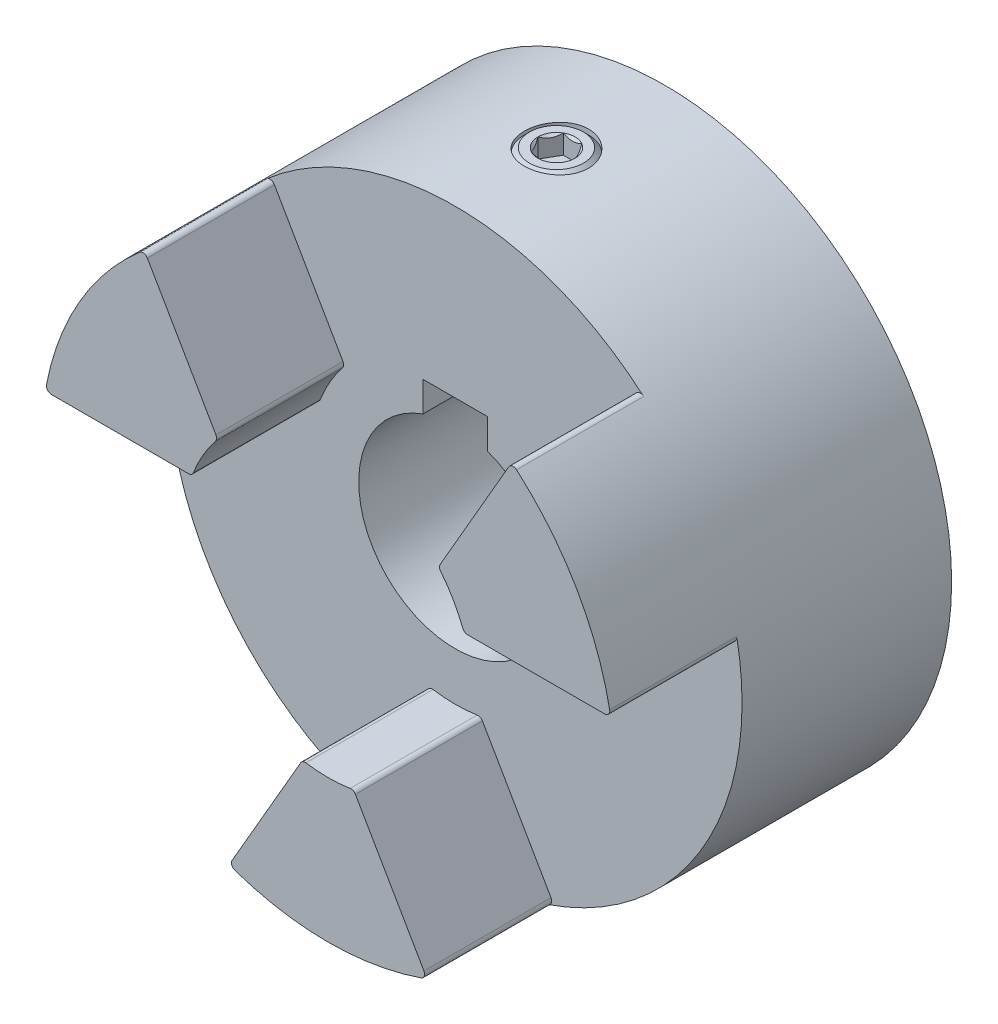
SolidWorks part; units mm, degrees
ref_plane "Front" through (0, 0, 0) normal (0, 0, 1) x (1, 0, 0)
ref_plane "Top" through (0, 0, 0) normal (0, 1, 0) x (1, 0, 0)
ref_plane "Right" through (0, 0, 0) normal (1, 0, 0) x (0, 0, -1)
sketch "Sketch3" plane through (0, 0, 0) normal (1, 0, 0) x (0, 0, -1)
  line L0 (27.3844, 0) -> (-27.3844, 0) construction
  circle A0 centre (0, 0) radius 5.1149 construction
  circle A1 centre (0, 0) radius 9 construction
  circle A2 centre (0, 0) radius 26.7891 construction
  point P7 (0, 5.1149)
  point P8 (0, -5.1149)
  point P9 (0, 9)
  point P10 (0, -9)
  point P11 (0, 26.7891)
  point P12 (0, -26.7891)
  point P13 (6.7469, 0)
  point P14 (-5.1149, 0)
  point P15 (5.1149, 0)
  point P16 (-5.1149, 26.7891)
  point P17 (27.3844, 26.7891)
  point P18 (6.7469, 26.7891)
  dimension "OD" = 53.5781
  dimension "Shaft Dia" = 18
  dimension "Overall Lg" = 54.7687
  dimension "Bore Depth" = 20.6375
  dimension "Lug Lg" = 11.8618
sketch "Sketch1" plane through (0, 0, 0) normal (0, 0, 1) x (1, 0, 0)
  circle A0 centre (0, 0) radius 26.7891
  circle A1 centre (0, 0) radius 9 construction
extrude "Boss-Extrude1" add sketch "Sketch1" against normal up to vertex (27.3844 mm away) from vertex up to point (0, 0, -27.3844) starting at point (0, 0, -6.7469)
sketch "Sketch10" [suppressed] plane through (0, 0, -3.5719) normal (0, 0, 1) x (1, 0, 0)
  arc A14 (-1.0963, -4.1108) -> (1.0963, -4.1108) centre (0, 0) ccw
  arc A15 (-3.4409, -7.1529) -> (-1.0963, -4.1108) centre (-9.5758, 0) ccw
  arc A19 (1.0963, -4.1108) -> (3.4409, -7.1529) centre (9.5758, 0) ccw
  circle A32 centre (0, 0) radius 7.9375 construction
  arc A33 (-3.4409, -7.1529) -> (3.4409, -7.1529) centre (0, 0) ccw
  point P0 (0, -4.2545)
  point P1 (0, -7.9375)
  dimension "D1" = 3.683
  dimension "D4" = 9.4234
  dimension "D2" = 6.8819
  dimension "D3" = 2.1926
extrude "Boss-Extrude4" [suppressed] add sketch "Sketch10" along normal up to vertex up to point (0, 0, 5.1149)
fillet "Fillet2" [suppressed] radius 0.381
other "Move Face3" [suppressed] parameters "D1"=90
pattern_circular "CirPattern2" [suppressed] count 2 over 360 of bodies 116
sketch "Sketch11" [suppressed] plane through (0, 0, -5.9531) normal (0, 0, 1) x (1, 0, 0)
  arc A0 (-1.5825, -7.8835) -> (1.5738, -7.8835) centre (-0.0044, -0.0397) ccw
  arc A1 (-1.5825, -7.8835) -> (-2.9616, -8.354) centre (-1.8681, -9.3029) ccw
  arc A2 (-2.9616, -8.354) -> (-4.9794, -11.8231) centre (5.1535, -15.3956) ccw
  arc A3 (-4.9794, -11.8231) -> (-4.4308, -12.9555) centre (-4.1442, -12.1175) ccw
  arc A4 (-4.4308, -12.9555) -> (4.4176, -12.96) centre (0, 0) ccw
  arc A5 (4.4176, -12.96) -> (4.9692, -11.8231) centre (4.1308, -12.1185) ccw
  arc A6 (4.9692, -11.8231) -> (2.9523, -8.354) centre (-5.1643, -15.3938) ccw
  arc A7 (2.9523, -8.354) -> (1.5738, -7.8835) centre (1.8592, -9.3021) ccw
  circle A8 centre (0, 0) radius 13.6922 construction
  point P18 (-0.007, -13.6922)
  point P19 (-0.0044, -8.0407)
  dimension "D1" = 1.4478
  dimension "D2" = 8.001
  dimension "D3" = 10.7442
  dimension "D4" = 0.889
  dimension "D9" = 5.6515
  dimension "D5" = 5.072
  dimension "D6" = 3.1563
  dimension "D7" = 5.9139
  dimension "D8" = 9.9486
extrude "Boss-Extrude5" [suppressed] add sketch "Sketch11" along normal up to vertex up to point (0, 0, 5.1149)
other "Move Face1" [suppressed] parameters "D1"=90
pattern_circular "CirPattern3" [suppressed] count 2 over 360 of bodies 118
sketch "Sketch12" [suppressed] plane through (0, 0, -6.1516) normal (0, 0, 1) x (1, 0, 0)
  line L0 (-5.1097, -10.267) -> (-8.533, -13.6894)
  line L1 (8.533, -13.6894) -> (5.1097, -10.267)
  arc A0 (-2.3442, -9.4968) -> (2.3442, -9.4968) centre (0, 0) ccw
  arc A1 (-2.3442, -9.4968) -> (-5.1097, -10.267) centre (-3.0443, -12.333) ccw
  arc A2 (-8.533, -13.6894) -> (-8.3299, -15.1215) centre (-7.8934, -14.3292) ccw
  arc A3 (-8.3299, -15.1215) -> (8.3299, -15.1215) centre (0, 0) ccw
  arc A4 (8.3299, -15.1215) -> (8.533, -13.6894) centre (7.8934, -14.3292) ccw
  arc A5 (5.1097, -10.267) -> (2.3442, -9.4968) centre (3.0443, -12.333) ccw
  circle A6 centre (0, 0) radius 17.2641 construction
  point P16 (0, -9.7819)
  point P17 (0, -17.2641)
  dimension "D1" = 7.4822
  dimension "D2" = 10.2193
  dimension "D3" = 4.6884
  dimension "D4" = 17.066
  dimension "D5" = 16.6598
extrude "Boss-Extrude6" [suppressed] add sketch "Sketch12" along normal up to vertex up to point (0, 0, 5.1149)
other "Move Face2" [suppressed] parameters "D1"=90
pattern_circular "CirPattern4" [suppressed] count 2 over 360 of bodies 120
sketch "Sketch2" plane through (0, 0, -6.7469) normal (0, 0, 1) x (1, 0, 0)
  line L0 (-9.2385, -25.1456) -> (-2.385, -13.2749)
  line L2 (2.385, -13.2749) -> (9.2385, -25.1456)
  circle A0 centre (0, 0) radius 26.7891 construction
  arc A1 (-9.2385, -25.1456) -> (9.2385, -25.1456) centre (0, 0) ccw
  arc A2 (-2.385, -13.2749) -> (2.385, -13.2749) centre (0, 0) ccw
  circle A3 centre (0, 0) radius 4.572 construction
  dimension "Spider Inner body Dia" = 26.9748
  dimension "Spider Leg Thickness" = 9.144
  dimension "D4" = 4.7699
  dimension "D1" = 60
extrude "Boss-Extrude2" add sketch "Sketch2" along normal up to vertex (11.8618 mm away) up to point (0, 0, 5.1149)
fillet "Fillet1" radius 0.477 4 edges at (2.385, -13.2749, -0.816) (-2.385, -13.2749, -0.816)
pattern_circular "CirPattern1" count 3 over 360 about axis through (0, 0, -27.3844) along (0, 0, 1) of "Boss-Extrude2", "Fillet1"
sketch "Sketch15" plane through (0, 0, 0) normal (0, 0, 1) x (1, 0, 0)
  circle A0 centre (0, 0) radius 9
extrude "Cut-Extrude5" cut sketch "Sketch15" against normal through all and the other way through all
chamfer "Chamfer1" distance 1.0716 angle 56 2 edges at (26.7891, 0, -27.3844) (9, 0, -27.3844) first distance on face at (26.7891, 0, -27.3844) first distance on face at (9, 0, -6.7469)
sketch "Sketch4" plane through (0, 0, 0) normal (0, 0, 1) x (1, 0, 0)
  line L1 (-3, 11.2853) -> (3, 11.2853)
  line L2 (-3, 11.2853) -> (-3, 8.4853)
  line L4 (3, 11.2853) -> (3, 8.4853)
  arc A1 (3, 8.4853) -> (-3, 8.4853) centre (0, 0) ccw
  circle A2 centre (0, 0) radius 9 construction
  dimension "Keyway Ht" = 2.8
  dimension "Keyway Wd" = 6
extrude "Cut-Extrude1" cut sketch "Sketch4" against normal through all and the other way through all
sketch "Sketch5" plane through (0, 0, 0) normal (0, 1, 0) x (1, 0, 0)
  line L1 (0, -46.4939) -> (0, 46.4939) construction
  circle A0 centre (0, 16.2084) radius 3
  dimension "Screw Dia" = 6
  dimension "Screw Offset" = 11.176
extrude "Cut-Extrude2" cut sketch "Sketch5" along normal through all
ref_plane "Plane1" through (0, 26.7891, 0) normal (0, 1, 0) x (-1, 0, 0)
sketch "Sketch6" plane through (0, 26.7891, 0) normal (0, 1, 0) x (-1, 0, 0)
  circle A1 centre (0, -16.2084) radius 3
  circle A2 centre (0, -16.2084) radius 3
  dimension "D1" = 0
extrude "Boss-Extrude3" add sketch "Sketch6" against normal blind 8 separate body
sketch "Sketch8" plane through (0, 26.7891, 0) normal (0, 1, 0) x (1, 0, 0)
  line L1 (0.866, 14.7084) -> (1.7321, 16.2084)
  line L2 (1.7321, 16.2084) -> (0.866, 17.7084)
  line L3 (0.866, 17.7084) -> (-0.866, 17.7084)
  line L4 (-0.866, 17.7084) -> (-1.7321, 16.2084)
  line L5 (-1.7321, 16.2084) -> (-0.866, 14.7084)
  line L6 (-0.866, 14.7084) -> (0.866, 14.7084)
  circle A0 centre (0, 16.2084) radius 1.5 construction
  dimension "D1" = 3
extrude "Cut-Extrude3" cut sketch "Sketch8" against normal blind 1.8
sketch "Sketch9" plane through (0, 26.7891, 0) normal (0, 1, 0) x (1, 0, 0)
  circle A0 centre (0, 16.2084) radius 1.7321
extrude "Cut-Extrude4" cut sketch "Sketch9" against normal through all draft 45
chamfer "Chamfer3" distance 0.48 angle 45 1 edges at (0, 26.7891, -13.2084)
chamfer "Chamfer4" distance 1.02 angle 45 1 edges at (0, 18.7891, -13.2084)
sketch "Sketch16" [suppressed] plane through (0, 0, -61.9125) normal (0, 0, -1) x (-1, 0, 0)
  circle A0 centre (0, 0) radius 50.8
  dimension "D1" = 101.6
extrude "Cut-Extrude6" [suppressed] cut sketch "Sketch16" against normal blind 30.3022 flip side to cut
chamfer "Chamfer5" [suppressed] distance 1.778 angle 56
fillet "Fillet3" [suppressed] radius 1.27
move or copy body "Body-Move/Copy1" [suppressed] bodies to move or copy 115 copy no translate (0, -6.35, 0)
sketch "Sketch17" [suppressed] plane through (0, 0, -67.8656) normal (0, 0, -1) x (-1, 0, 0)
  circle A0 centre (0, 0) radius 53.975
  dimension "D1" = 107.95
extrude "Cut-Extrude7" [suppressed] cut sketch "Sketch17" against normal blind 36.576 flip side to cut
move or copy body "Body-Move/Copy2" [suppressed] bodies to move or copy 115 copy no translate (0, -9.525, 0)
fillet "Fillet4" [suppressed] radius 2.54
fillet "Fillet5" [suppressed] radius 1.27
equation "\"D1@Chamfer1\" = \"OD@Sketch3\" * .02"
equation "\"D1@Fillet1\" = \"D4@Sketch2\" * .1"
equation "\"D1@Sketch8\" = \"Screw Dia@Sketch5\" * .5"
equation "\"D1@Cut-Extrude3\" = \"Screw Dia@Sketch5\" * .3"
equation "\"D1@Chamfer3\" = \"Screw Dia@Sketch5\" * .08"
equation "\"D1@Chamfer4\" = \"Screw Dia@Sketch5\" * .17"
